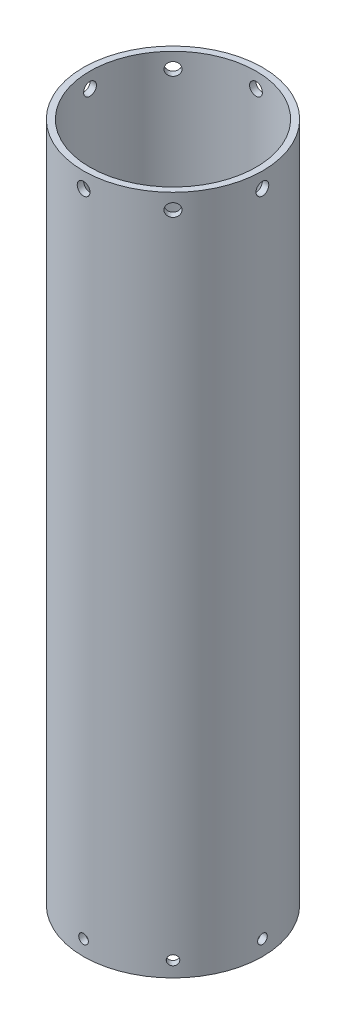
SolidWorks part; units mm, degrees
material "1060 Alloy"
ref_plane "Front Plane" through (0, 0, 0) normal (0, 0, 1) x (1, 0, 0)
ref_plane "Top Plane" through (0, 0, 0) normal (0, 1, 0) x (1, 0, 0)
ref_plane "Right Plane" through (0, 0, 0) normal (1, 0, 0) x (0, 0, -1)
sketch "Sketch2" plane through (0, 0, 0) normal (0, 0, 1) x (1, 0, 0)
  line L0 (0, 0) -> (0, 365.76) construction
  line L3 (41.275, 0) -> (44.45, 0)
  line L5 (41.275, 337.566) -> (44.45, 337.566)
  line L6 (44.45, 0) -> (44.45, 337.566)
  line L11 (41.275, 337.566) -> (41.275, 168.783)
  line L12 (41.275, 168.783) -> (41.2565, 168.7573)
  line L13 (41.275, 168.783) -> (41.275, 0)
  line L14 (0, -55) -> (0, 55) construction
  point P2 (0, 0)
  point P8 (0, 0)
  dimension "D3" = 3.175
  dimension "D4" = 337.566
revolve "Revolve1" add sketch "Sketch2" angle 360 about L0 region at (42.8625, 168.783, 0)
ref_axis "Axis1" through (0, -17.0472, 0) along (0, 1, 0)
ref_plane "Plane1" through (0, 7.62, 0) normal (0, -1, 0) x (-1, 0, 0)
ref_axis "Axis2" through (0, 7.62, 88.99) along (0, 0, -1)
hole_wizard "3/16 (0.1875) Diameter Hole1" positions "3DSketch1" profile "Sketch3" hole size "3/16" standard "ANSI Inch" end condition up to next
sketch3d "3DSketch1"
  line L0 (0, 7.62, 88.99) -> (0, 7.62, -88.99) construction
  point P0 (0, 7.62, -44.45)
sketch "Sketch3" plane through (0, 7.62, -44.45) normal (1, 0, 0) x (0, 1, 0)
  line L0 (0, 0) -> (0, 3.175)
  line L1 (0, 3.175) -> (2.3812, 3.175)
  line L2 (2.3812, 3.175) -> (2.3812, 0)
  line L5 (2.3812, 0) -> (0, 0)
  line L11 (0, -6.35) -> (0, 107.95) construction
  dimension "Thru Hole Dia." = 4.7625
  dimension "Thru Hole Depth" = 3.175
pattern_circular "CirPattern1" count 8 over 360 about axis through (0, -17.0472, 0) along (0, 1, 0) of "3/16 (0.1875) Diameter Hole1"
ref_plane "Plane2" through (0, 329.946, 0) normal (0, 1, 0) x (1, 0, 0)
ref_axis "Axis3" through (0, 329.946, -48.895) along (0, 0, 1)
hole_wizard "1/4 (0.25) Diameter Hole1" positions "3DSketch3" profile "Sketch5" hole size "1/4" standard "ANSI Inch"
sketch3d "3DSketch3"
  line L0 (0, 329.946, -48.895) -> (0, 329.946, 48.895) construction
  point P0 (0, 329.946, 44.45)
  point P3 (0, 0, 0)
sketch "Sketch5" plane through (0, 329.946, 44.45) normal (1, 0, 0) x (0, -1, 0)
  line L0 (0, 0) -> (0, 13.5917)
  line L1 (0, 13.5917) -> (3.175, 11.684)
  line L2 (3.175, 11.684) -> (3.175, 0)
  line L5 (3.175, 0) -> (0, 0)
  line L10 (0, 13.5917) -> (-3.175, 11.684) construction
  line L11 (0, -6.35) -> (0, 107.95) construction
  dimension "Hole Dia." = 6.35
  dimension "Hole Depth" = 11.684
  dimension "Drill Angle" = 118
pattern_circular "CirPattern2" count 8 over 360 about axis through (0, -17.0472, 0) along (0, 1, 0) of "1/4 (0.25) Diameter Hole1"
